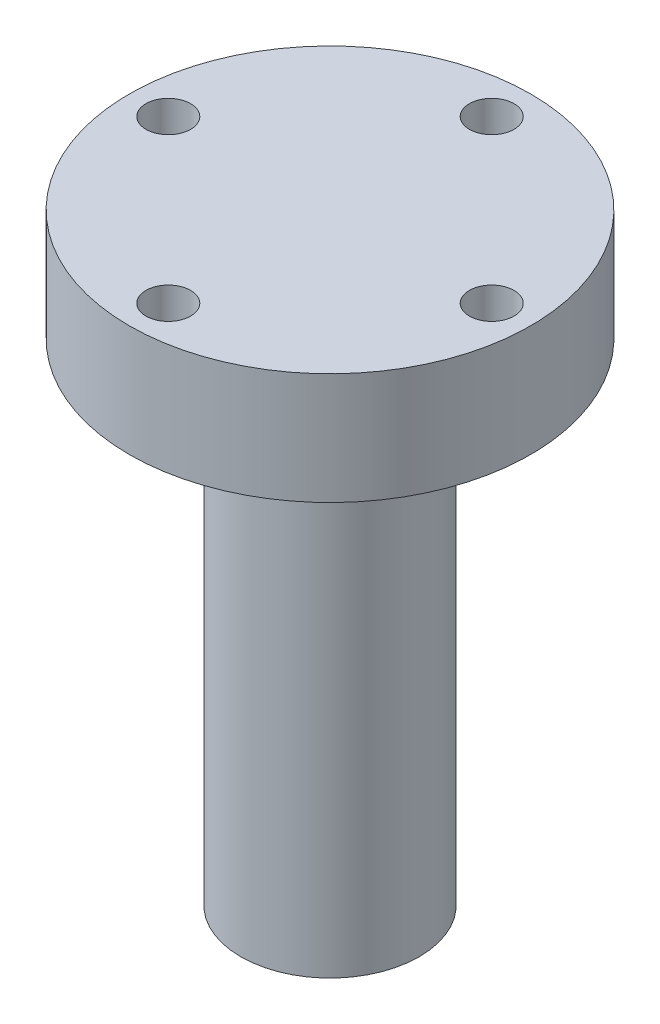
SolidWorks part; units mm, degrees
ref_plane "Front Plane" through (0, 0, 0) normal (0, 0, 1) x (1, 0, 0)
ref_plane "Top Plane" through (0, 0, 0) normal (0, 1, 0) x (1, 0, 0)
ref_plane "Right Plane" through (0, 0, 0) normal (1, 0, 0) x (0, 0, -1)
sketch "Sketch1" plane through (0, 0, 0) normal (0, 1, 0) x (1, 0, 0)
  circle A0 centre (0, 0) radius 9
  dimension "D1" = 18
extrude "BracketMount" add sketch "Sketch1" along normal blind 5
sketch "Sketch2" plane through (0, 5, 0) normal (0, 1, 0) x (1, 0, 0)
  circle A0 centre (0, 7.25) radius 1
  circle A7 centre (7.25, 0) radius 1
  circle A8 centre (0, -7.25) radius 1
  circle A9 centre (-7.25, 0) radius 1
  point P19 (0, 0)
  dimension "D1" = 2
  dimension "D3" = 7.25
  dimension "D2" = 4
extrude "Bracket-MountHoles" cut sketch "Sketch2" against normal up to surface (5 mm away) up to face at (0, 0, 9)
sketch "Sketch3" plane through (0, 0, 0) normal (0, -1, 0) x (1, 0, 0)
  circle A0 centre (0, 0) radius 4
  dimension "D1" = 8
extrude "StepperSleeve" add sketch "Sketch3" along normal blind 22
sketch "Sketch5" plane through (0, -22, 0) normal (0, -1, 0) x (1, 0, 0)
  line L3 (1.92, 1.7532) -> (1.92, -1.7532)
  circle A0 centre (0, 0) radius 4 construction
  arc A6 (1.92, 1.7532) -> (1.92, -1.7532) centre (0, 0) ccw
  point P7 (-2.6, 0)
  dimension "D2" = 2.6
  dimension "D1" = 4.52
extrude "OrientationNub" cut sketch "Sketch5" against normal up to surface (22 mm away) up to face at (0, 0, 4)
